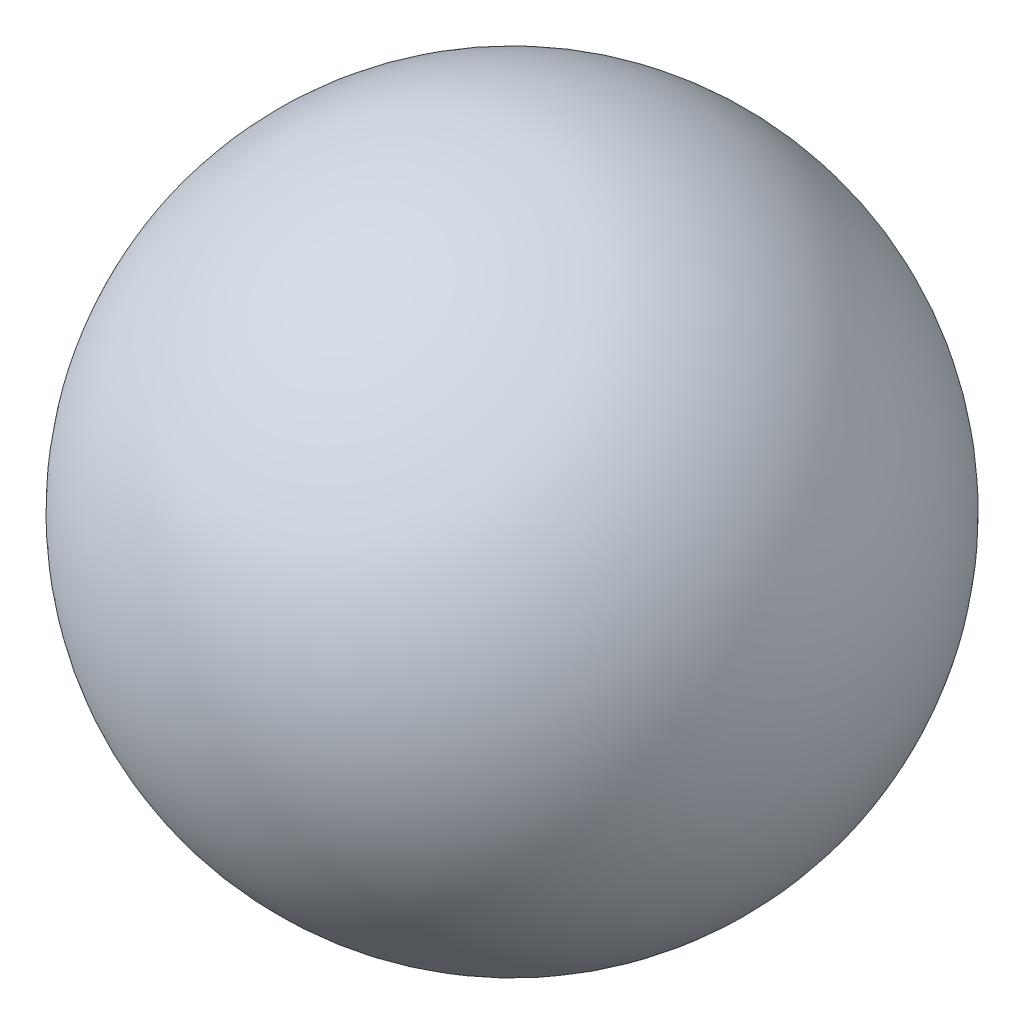
SolidWorks part; units mm, degrees
ref_plane "Front Plane" through (0, 0, 0) normal (0, 0, 1) x (1, 0, 0)
ref_plane "Top Plane" through (0, 0, 0) normal (0, 1, 0) x (1, 0, 0)
ref_plane "Right Plane" through (0, 0, 0) normal (1, 0, 0) x (0, 0, -1)
sketch "Sketch1" plane through (0, 0, 0) normal (0, 0, 1) x (1, 0, 0)
  line L0 (0, 0) -> (2.2, 0)
  line L1 (0, 0) -> (-2.2, 0)
  arc A0 (2.2, 0) -> (-2.2, 0) centre (0, 0) ccw
  dimension "D1" = 4.4
revolve "Revolve1" add sketch "Sketch1" angle 360 about L1
scale "Scale1" bodies to scale 101 scale about centroid uniform scaling yes scale factor 6
scale "Scale2" scale about centroid uniform scaling yes scale factor 3.323882
scale "Scale3" bodies to scale 103 scale about centroid uniform scaling yes scale factor 0.416653
scale "Scale4" bodies to scale 104 scale about centroid uniform scaling yes scale factor 0.705392
scale "Scale5" bodies to scale 105 scale about centroid uniform scaling yes scale factor 0.666667
